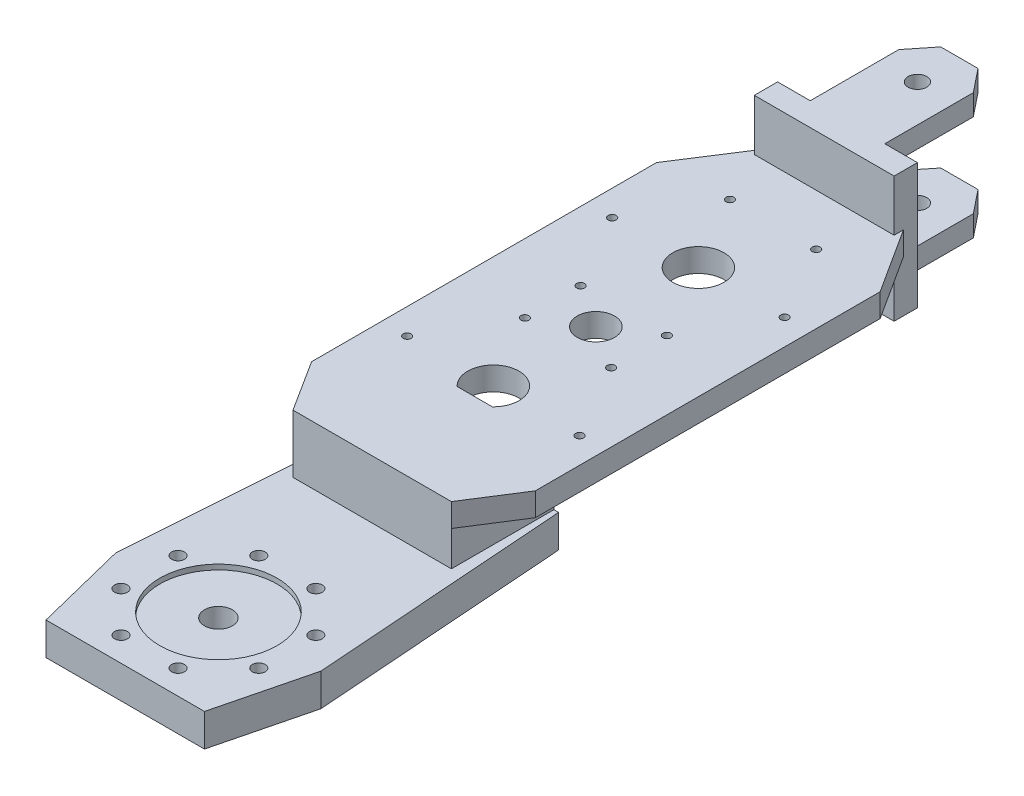
SolidWorks part; units mm, degrees
ref_plane "Front Plane" through (0, 0, 0) normal (0, 0, 1) x (1, 0, 0)
ref_plane "Top Plane" through (0, 0, 0) normal (0, 1, 0) x (1, 0, 0)
ref_plane "Right Plane" through (0, 0, 0) normal (1, 0, 0) x (0, 0, -1)
ref_plane "PL_Knee_Plate_base" through (0, -34, 0) normal (0, 1, 0) x (1, 0, 0)
sketch "SK_Knee_Plate" plane through (0, -34, 0) normal (0, 1, 0) x (1, 0, 0)
  line L0 (-34, -40) -> (34, -40)
  line L1 (34, -40) -> (44, 0)
  line L2 (44, 0) -> (36, 110)
  line L3 (36, 110) -> (-36, 110)
  line L4 (-36, 110) -> (-44, 0)
  line L5 (-44, 0) -> (-34, -40)
  circle A0 centre (29.5641, 12.2459) radius 2.75
  circle A1 centre (12.2459, 29.5641) radius 2.75
  circle A2 centre (-12.2459, 29.5641) radius 2.75
  circle A3 centre (-29.5641, 12.2459) radius 2.75
  circle A4 centre (-29.5641, -12.2459) radius 2.75
  circle A5 centre (-12.2459, -29.5641) radius 2.75
  circle A6 centre (12.2459, -29.5641) radius 2.75
  circle A7 centre (29.5641, -12.2459) radius 2.75
  circle A8 centre (0, 0) radius 6
  dimension "D11_SK_Knee_Plate" = 5.5
  dimension "D14_SK_Knee_Plate" = 5.5
  dimension "D17_SK_Knee_Plate" = 5.5
  dimension "D20_SK_Knee_Plate" = 5.5
  dimension "D23_SK_Knee_Plate" = 5.5
  dimension "D26_SK_Knee_Plate" = 5.5
  dimension "D29_SK_Knee_Plate" = 5.5
  dimension "D32_SK_Knee_Plate" = 5.5
  dimension "D35_SK_Knee_Plate" = 12
  dimension "P1" = 34
  dimension "P2" = 40
  dimension "P3" = 34
  dimension "P4" = 40
  dimension "P5" = 44
  dimension "P6" = 36
  dimension "P7" = 110
  dimension "P8" = 36
  dimension "P9" = 110
  dimension "P10" = 44
  dimension "P12" = 29.5641
  dimension "P13" = 12.2459
  dimension "P15" = 12.2459
  dimension "P16" = 29.5641
  dimension "P18" = 12.2459
  dimension "P19" = 29.5641
  dimension "P21" = 29.5641
  dimension "P22" = 12.2459
  dimension "P24" = 29.5641
  dimension "P25" = 12.2459
  dimension "P27" = 12.2459
  dimension "P28" = 29.5641
  dimension "P30" = 12.2459
  dimension "P31" = 29.5641
  dimension "P33" = 29.5641
  dimension "P34" = 12.2459
extrude "Knee_Plate" add sketch "SK_Knee_Plate" along normal blind 14
ref_plane "PL_Knee_Pilot_Recess_base" through (0, -20, 0) normal (0, 1, 0) x (1, 0, 0)
sketch "SK_Knee_Pilot_Recess" plane through (0, -20, 0) normal (0, 1, 0) x (1, 0, 0)
  circle A0 centre (0, 0) radius 25.15
  dimension "D1_SK_Knee_Pilot_Recess" = 50.3
extrude "Knee_Pilot_Recess" cut sketch "SK_Knee_Pilot_Recess" against normal blind 2.2
ref_plane "PL_Joggle_base" through (0, 0, -110) normal (0, 0, 1) x (1, 0, 0)
sketch "SK_Joggle" plane through (0, 0, -110) normal (0, 0, 1) x (1, 0, 0)
  line L0 (-34, -34) -> (34, -34)
  line L1 (34, -34) -> (34, 5)
  line L2 (34, 5) -> (-34, 5)
  line L3 (-34, 5) -> (-34, -34)
  dimension "P1" = 34
  dimension "P2" = 34
  dimension "P3" = 34
  dimension "P4" = 34
  dimension "P5" = 34
  dimension "P6" = 5
  dimension "P7" = 34
  dimension "P8" = 5
extrude "Joggle" add sketch "SK_Joggle" along normal blind 44
ref_plane "PL_Web_base" through (0, -5, 0) normal (0, 1, 0) x (1, 0, 0)
sketch "SK_Web" plane through (0, -5, 0) normal (0, 1, 0) x (1, 0, 0)
  line L0 (-34, 66) -> (34, 66)
  line L1 (34, 66) -> (48, 88)
  line L2 (48, 88) -> (48, 236)
  line L3 (48, 236) -> (30, 264)
  line L4 (30, 264) -> (-30, 264)
  line L5 (-30, 264) -> (-48, 236)
  line L6 (-48, 236) -> (-48, 88)
  line L7 (-48, 88) -> (-34, 66)
  circle A0 centre (37, 118) radius 1.7
  circle A1 centre (18.5, 150.0429) radius 1.7
  circle A2 centre (-18.5, 150.0429) radius 1.7
  circle A3 centre (-37, 118) radius 1.7
  circle A4 centre (-18.5, 85.9571) radius 1.7
  circle A5 centre (18.5, 85.9571) radius 1.7
  circle A6 centre (37, 206) radius 1.7
  circle A7 centre (18.5, 238.0429) radius 1.7
  circle A8 centre (-18.5, 238.0429) radius 1.7
  circle A9 centre (-37, 206) radius 1.7
  circle A10 centre (-18.5, 173.9571) radius 1.7
  circle A11 centre (18.5, 173.9571) radius 1.7
  circle A12 centre (0, 118) radius 11
  circle A13 centre (0, 206) radius 11
  circle A14 centre (0, 162) radius 8
  dimension "D17_SK_Web" = 3.4
  dimension "D20_SK_Web" = 3.4
  dimension "D23_SK_Web" = 3.4
  dimension "D26_SK_Web" = 3.4
  dimension "D29_SK_Web" = 3.4
  dimension "D32_SK_Web" = 3.4
  dimension "D35_SK_Web" = 3.4
  dimension "D38_SK_Web" = 3.4
  dimension "D41_SK_Web" = 3.4
  dimension "D44_SK_Web" = 3.4
  dimension "D47_SK_Web" = 3.4
  dimension "D50_SK_Web" = 3.4
  dimension "D53_SK_Web" = 22
  dimension "D55_SK_Web" = 22
  dimension "D57_SK_Web" = 16
  dimension "P1" = 34
  dimension "P2" = 66
  dimension "P3" = 34
  dimension "P4" = 66
  dimension "P5" = 48
  dimension "P6" = 88
  dimension "P7" = 48
  dimension "P8" = 236
  dimension "P9" = 30
  dimension "P10" = 264
  dimension "P11" = 30
  dimension "P12" = 264
  dimension "P13" = 48
  dimension "P14" = 236
  dimension "P15" = 48
  dimension "P16" = 88
  dimension "P18" = 37
  dimension "P19" = 118
  dimension "P21" = 18.5
  dimension "P22" = 150.0429
  dimension "P24" = 18.5
  dimension "P25" = 150.0429
  dimension "P27" = 37
  dimension "P28" = 118
  dimension "P30" = 18.5
  dimension "P31" = 85.9571
  dimension "P33" = 18.5
  dimension "P34" = 85.9571
  dimension "P36" = 37
  dimension "P37" = 206
  dimension "P39" = 18.5
  dimension "P40" = 238.0429
  dimension "P42" = 18.5
  dimension "P43" = 238.0429
  dimension "P45" = 37
  dimension "P46" = 206
  dimension "P48" = 18.5
  dimension "P49" = 173.9571
  dimension "P51" = 18.5
  dimension "P52" = 173.9571
  dimension "P54" = 118
  dimension "P56" = 206
  dimension "P58" = 162
extrude "Web" add sketch "SK_Web" along normal blind 10
ref_plane "PL_Fork_Bar_base" through (0, 0, -270) normal (0, 0, 1) x (1, 0, 0)
sketch "SK_Fork_Bar" plane through (0, 0, -270) normal (0, 0, 1) x (1, 0, 0)
  line L0 (-30, -27) -> (30, -27)
  line L1 (30, -27) -> (30, 27)
  line L2 (30, 27) -> (-30, 27)
  line L3 (-30, 27) -> (-30, -27)
  dimension "P1" = 30
  dimension "P2" = 27
  dimension "P3" = 30
  dimension "P4" = 27
  dimension "P5" = 30
  dimension "P6" = 27
  dimension "P7" = 30
  dimension "P8" = 27
extrude "Fork_Bar" add sketch "SK_Fork_Bar" along normal blind 10
ref_plane "PL_Tine_Lat_base" through (0, 18, 0) normal (0, 1, 0) x (1, 0, 0)
sketch "SK_Tine_Lat" plane through (0, 18, 0) normal (0, 1, 0) x (1, 0, 0)
  line L0 (-16, 260) -> (16, 260)
  line L1 (16, 260) -> (16, 308)
  line L2 (16, 308) -> (8, 318)
  line L3 (8, 318) -> (-8, 318)
  line L4 (-8, 318) -> (-16, 308)
  line L5 (-16, 308) -> (-16, 260)
  circle A0 centre (0, 300) radius 4
  dimension "D13_SK_Tine_Lat" = 8
  dimension "P1" = 16
  dimension "P2" = 260
  dimension "P3" = 16
  dimension "P4" = 260
  dimension "P5" = 16
  dimension "P6" = 308
  dimension "P7" = 8
  dimension "P8" = 318
  dimension "P9" = 8
  dimension "P10" = 318
  dimension "P11" = 16
  dimension "P12" = 308
  dimension "P14" = 300
extrude "Tine_Lat" add sketch "SK_Tine_Lat" along normal blind 9
ref_plane "PL_Tine_Med_base" through (0, -27, 0) normal (0, 1, 0) x (1, 0, 0)
sketch "SK_Tine_Med" plane through (0, -27, 0) normal (0, 1, 0) x (1, 0, 0)
  line L0 (-16, 260) -> (16, 260)
  line L1 (16, 260) -> (16, 308)
  line L2 (16, 308) -> (8, 318)
  line L3 (8, 318) -> (-8, 318)
  line L4 (-8, 318) -> (-16, 308)
  line L5 (-16, 308) -> (-16, 260)
  circle A0 centre (0, 300) radius 4
  dimension "D13_SK_Tine_Med" = 8
  dimension "P1" = 16
  dimension "P2" = 260
  dimension "P3" = 16
  dimension "P4" = 260
  dimension "P5" = 16
  dimension "P6" = 308
  dimension "P7" = 8
  dimension "P8" = 318
  dimension "P9" = 8
  dimension "P10" = 318
  dimension "P11" = 16
  dimension "P12" = 308
  dimension "P14" = 300
extrude "Tine_Med" add sketch "SK_Tine_Med" along normal blind 9
ref_plane "PL_AnkleZ" through (0, 0, -300) normal (0, 0, 1) x (1, 0, 0)
ref_axis "AX_AnklePitch" through (0, 30.05, -300) along (0, -1, 0)
ref_axis "AX_KneeY" through (0, 30.05, 0) along (0, -1, 0)
ref_plane "PL_KneeRef" through (0, 0, 0) normal (-0.9239, 0, 0.3827) x (0, -1, 0)
equation "\"Shin_length\" = 300"
equation "\"AnkleA_z\" = -118"
equation "\"AnkleB_z\" = -206"
